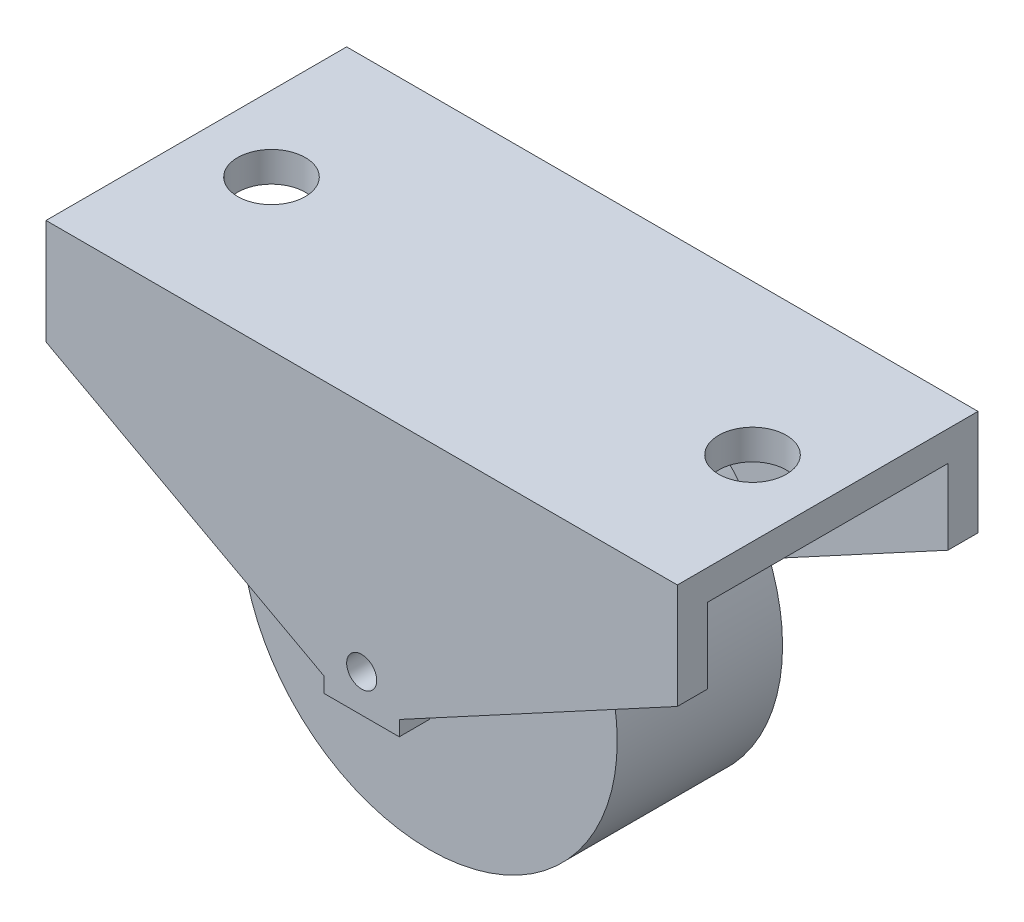
SolidWorks part; units mm, degrees
ref_plane "Спереди" through (0, 0, 0) normal (0, 0, 1) x (1, 0, 0)
ref_plane "Сверху" through (0, 0, 0) normal (0, 1, 0) x (1, 0, 0)
ref_plane "Справа" through (0, 0, 0) normal (1, 0, 0) x (0, 0, -1)
sketch "Эскиз1" plane through (0, 0, 0) normal (0, 1, 0) x (1, 0, 0)
  line L1 (-21, -10) -> (21, -10)
  line L2 (-21, -10) -> (-21, 10)
  line L3 (-21, 10) -> (21, 10)
  line L5 (-21, -10) -> (21, 10) construction
  line L6 (-21, 10) -> (21, -10) construction
  line L9 (-16, 0) -> (16, 0) construction
  line L10 (21, -10) -> (21, 10)
  circle A4 centre (-16, 0) radius 2.25
  circle A5 centre (16, 0) radius 2.25
  point P0 (0, 0)
  point P11 (0, 0)
  dimension "D3" = 4.5
  dimension "D4" = 4.5
  dimension "D5" = 32
  dimension "D1" = 42
  dimension "D2" = 20
extrude "Бобышка-Вытянуть1" add sketch "Эскиз1" along normal blind 2
sketch "Эскиз2" plane through (0, 0, 0) normal (0, 0, 1) x (1, 0, 0)
  line L2 (-46.046, -26) -> (131.9496, -26) construction
  line L3 (-21, 2) -> (21, 2) construction
  circle A0 centre (0, -13.5) radius 12.5
  dimension "D1" = 25
  dimension "D3" = 28
extrude "Бобышка-Вытянуть2" add sketch "Эскиз2" along normal blind 11 from offset 5.5 separate body offset against normal yes
sketch "Эскиз3" plane through (0, 0, 10) normal (0, 0, 1) x (1, 0, 0)
  line L2 (-21, -5) -> (-2.5, -15)
  line L5 (-21, 0) -> (21, 0)
  line L6 (21, 0) -> (21, -5)
  line L7 (-21, 0) -> (-21, -5)
  line L8 (-12.0225, -10.078) -> (12.0225, -16.922) construction
  line L9 (-2.5, -16) -> (2.5, -16)
  line L10 (2.5, -16) -> (2.5, -15)
  line L11 (-2.5, -16) -> (-2.5, -15)
  line L12 (2.5, -15) -> (21, -5)
  circle A1 centre (0, -13.5) radius 12.5 construction
  point P8 (0, -13.5)
  point P10 (0, -13.5)
  dimension "D1" = 2.5
  dimension "D2" = 2.5
  dimension "D3" = 2.5
  dimension "D4" = 1
  dimension "D5" = 5
extrude "Бобышка-Вытянуть3" add sketch "Эскиз3" against normal blind 2
pattern_linear "Линейный массив1" count 2 spacing 18 along (0, 0, -1) of "Бобышка-Вытянуть3"
sketch "Эскиз4" plane through (0, 0, -8) normal (0, 0, 1) x (1, 0, 0)
  circle A0 centre (0, -13.5) radius 1
  dimension "D1" = 2
extrude "Вырез-Вытянуть1" cut sketch "Эскиз4" against normal through all both and the other way through all
